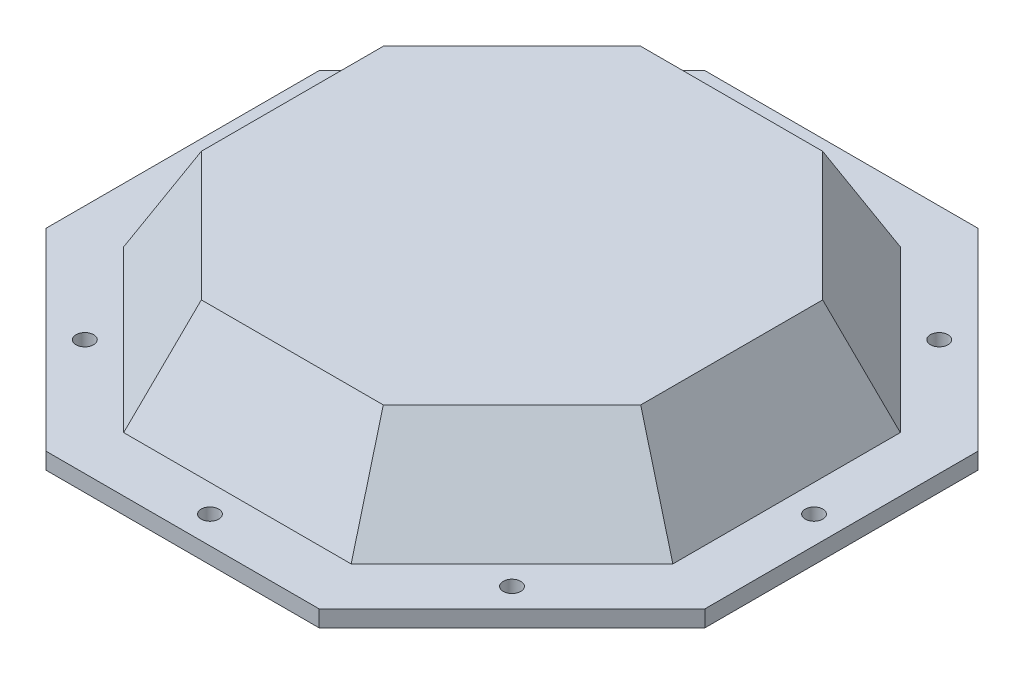
SolidWorks part; units mm, degrees
note: The reader was unsure of these and kept them because the rebuilt part matched: shared geometry of "Sketch3<3>".
material "ABS PC"
ref_plane "Front Plane" through (0, 0, 0) normal (0, 0, 1) x (1, 0, 0)
ref_plane "Top Plane" through (0, 0, 0) normal (0, 1, 0) x (1, 0, 0)
ref_plane "Right Plane" through (0, 0, 0) normal (1, 0, 0) x (0, 0, -1)
sketch "Sketch2" plane through (0, 0, 0) normal (0, 1, 0) x (1, 0, 0)
  line L1 (-60, -24.8528) -> (-24.8528, -60)
  line L2 (-24.8528, -60) -> (24.8528, -60)
  line L3 (24.8528, -60) -> (60, -24.8528)
  line L4 (60, -24.8528) -> (60, 24.8528)
  line L5 (60, 24.8528) -> (24.8528, 60)
  line L6 (24.8528, 60) -> (-24.8528, 60)
  line L7 (-24.8528, 60) -> (-60, 24.8528)
  line L8 (-60, 24.8528) -> (-60, -24.8528)
  circle A0 centre (0, 0) radius 60 construction
  circle A1 centre (-55, 0) radius 1.6
  circle A2 centre (55, 0) radius 1.6
  circle A3 centre (-38.8909, 38.8909) radius 1.6
  circle A4 centre (38.8909, -38.8909) radius 1.6
  circle A5 centre (0, 55) radius 1.6
  circle A6 centre (0, -55) radius 1.6
  circle A7 centre (38.8909, 38.8909) radius 1.6
  circle A8 centre (-38.8909, -38.8909) radius 1.6
  circle A9 centre (55, 0) radius 1.6
  circle A10 centre (-55, 0) radius 1.6
  circle A11 centre (38.8909, -38.8909) radius 1.6
  circle A12 centre (-38.8909, 38.8909) radius 1.6
  circle A13 centre (0, -55) radius 1.6
  circle A14 centre (0, 55) radius 1.6
  circle A15 centre (-38.8909, -38.8909) radius 1.6
  circle A16 centre (38.8909, 38.8909) radius 1.6
  point P45 (0, 0)
  dimension "D2" = 3.2
  dimension "D3" = 3.2
  dimension "D1" = 120
  dimension "D4" = 110
  dimension "D5" = 55
  dimension "D6" = 8
extrude "Boss-Extrude1" add sketch "Sketch2" along normal blind 3 contours L7 L8 L1 L2 L3 L4 L5 L6 A8 A7 A6 A5 A4 A3 A2 A1
sketch "Sketch3" plane through (0, 3, 0) normal (0, 1, 0) x (1, 0, 0)
  line L44 (-50, 20.7107) -> (-50, -20.7107)
  line L45 (-50, -20.7107) -> (-20.7107, -50)
  line L46 (-20.7107, -50) -> (20.7107, -50)
  line L47 (20.7107, -50) -> (50, -20.7107)
  line L48 (50, -20.7107) -> (50, 20.7107)
  line L49 (50, 20.7107) -> (20.7107, 50)
  line L50 (20.7107, 50) -> (-20.7107, 50)
  line L51 (-20.7107, 50) -> (-50, 20.7107)
  line L52 (-50, 20.7107) -> (-50, -20.7107)
  line L53 (-50, -20.7107) -> (-20.7107, -50)
  line L54 (-20.7107, -50) -> (20.7107, -50)
  line L55 (20.7107, -50) -> (50, -20.7107)
  line L56 (50, -20.7107) -> (50, 20.7107)
  line L57 (50, 20.7107) -> (20.7107, 50)
  line L58 (20.7107, 50) -> (-20.7107, 50)
  line L59 (-20.7107, 50) -> (-50, 20.7107)
  dimension "D1" = 10
extrude "Cut-Extrude1" cut sketch "Sketch3" against normal through all contours L58 L59 L52 L53 L54 L55 L56 L57
ref_plane "Plane1" through (0, 18, 0) normal (0, 1, 0) x (1, 0, 0)
sketch "Sketch4" plane through (0, 18, 0) normal (0, 1, 0) x (1, 0, 0)
  line L44 (-40, 16.5685) -> (-40, -16.5685)
  line L45 (-40, -16.5685) -> (-16.5685, -40)
  line L46 (-16.5685, -40) -> (16.5685, -40)
  line L47 (16.5685, -40) -> (40, -16.5685)
  line L48 (40, -16.5685) -> (40, 16.5685)
  line L49 (40, 16.5685) -> (16.5685, 40)
  line L50 (16.5685, 40) -> (-16.5685, 40)
  line L51 (-16.5685, 40) -> (-40, 16.5685)
  line L52 (-40, 16.5685) -> (-40, -16.5685)
  line L53 (-40, -16.5685) -> (-16.5685, -40)
  line L54 (-16.5685, -40) -> (16.5685, -40)
  line L55 (16.5685, -40) -> (40, -16.5685)
  line L56 (40, -16.5685) -> (40, 16.5685)
  line L57 (40, 16.5685) -> (16.5685, 40)
  line L58 (16.5685, 40) -> (-16.5685, 40)
  line L59 (-16.5685, 40) -> (-40, 16.5685)
  dimension "D1" = 10
extrude "Boss-Extrude2" add sketch "Sketch4" along normal blind 3 separate body
loft "Loft1" add profiles "Sketch3<3>" section "Sketch3<3>" section face at (0, 21, 0) connector at (-20.7107, 3, -50) connector at (-16.5685, 21, -40)
sketch "Sketch3<3>" plane through (0, 3, 0) normal (0, 1, 0) x (1, 0, 0) same geometry as "Sketch3"
shell "Shell1" thickness 2 removed face at (0, 3, 0)
sketch "Sketch5" plane through (0, 3, 0) normal (0, -1, 0) x (1, 0, 0)
  line L1 (-50, 20.7107) -> (-50, -20.7107)
  line L2 (-50, -20.7107) -> (-20.7107, -50)
  line L3 (-20.7107, -50) -> (20.7107, -50)
  line L4 (20.7107, -50) -> (50, -20.7107)
  line L5 (50, -20.7107) -> (50, 20.7107)
  line L6 (50, 20.7107) -> (20.7107, 50)
  line L7 (20.7107, 50) -> (-20.7107, 50)
  line L8 (-20.7107, 50) -> (-50, 20.7107)
  line L9 (-47.7121, 19.763) -> (-47.7121, -19.763)
  line L10 (-47.7121, -19.763) -> (-19.763, -47.7121)
  line L11 (-19.763, -47.7121) -> (19.763, -47.7121)
  line L12 (19.763, -47.7121) -> (47.7121, -19.763)
  line L13 (47.7121, -19.763) -> (47.7121, 19.763)
  line L14 (47.7121, 19.763) -> (19.763, 47.7121)
  line L15 (19.763, 47.7121) -> (-19.763, 47.7121)
  line L16 (-19.763, 47.7121) -> (-47.7121, 19.763)
  circle A0 centre (0, 0) radius 50 construction
  circle A1 centre (0, 0) radius 47.7121 construction
extrude "Boss-Extrude4" add sketch "Sketch5" along normal blind 3
